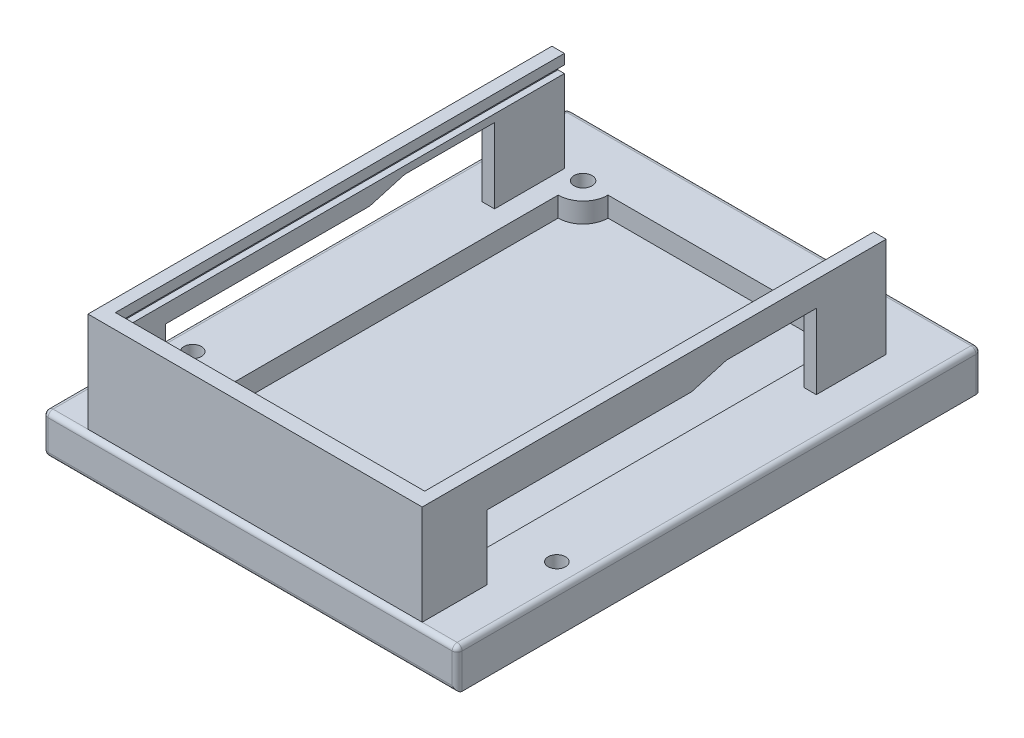
SolidWorks part; units mm, degrees
ref_plane "Front Plane" through (0, 0, 0) normal (0, 0, 1) x (1, 0, 0)
ref_plane "Top Plane" through (0, 0, 0) normal (0, 1, 0) x (1, 0, 0)
ref_plane "Right Plane" through (0, 0, 0) normal (1, 0, 0) x (0, 0, -1)
sketch "Sketch1" plane through (0, 0, 0) normal (0, 1, 0) x (1, 0, 0)
  line L0 (41.5, 95) -> (41.5, 0) construction
  line L1 (0, 0) -> (83, 0)
  line L2 (0, 0) -> (0, 105)
  line L3 (0, 105) -> (83, 105)
  line L4 (83, 0) -> (83, 105)
  line L5 (14.475, 93.775) -> (14.475, 11.225) construction
  circle A0 centre (5, 25) radius 1.75
  circle A1 centre (14.475, 11.225) radius 1.65 construction
  circle A2 centre (14.475, 93.775) radius 1.65 construction
  circle A3 centre (78, 25) radius 1.75
  circle A4 centre (68.525, 11.225) radius 1.65 construction
  circle A5 centre (68.525, 93.775) radius 1.65 construction
  point P19 (14.475, 52.5)
  point P20 (41.5, 0)
  point P21 (0, 52.5)
  dimension "D2" = 36.5
  dimension "D3" = 3.5
  dimension "D5" = 13.775
  dimension "D6" = 27.025
  dimension "D7" = 3.3
  dimension "D9" = 82.55
  dimension "D10" = 3.3
  dimension "D1" = 83
  dimension "D4" = 105
extrude "Boss-Extrude1" add sketch "Sketch1" along normal blind 8
sketch "Sketch3" plane through (0, 0, 0) normal (0, -1, 0) x (1, 0, 0)
  point P0 (14.475, -11.225)
  point P1 (68.525, -11.225)
  point P3 (68.525, -93.775)
  point P5 (14.475, -93.775)
hole_wizard "CBORE for M3 SHCS1" positions "Sketch3" profile "Sketch4" counterbore size "M3" standard "ANSI Metric" end condition through all
sketch "Sketch4" plane through (14.475, 0, -11.225) normal (1, 0, 0) x (0, 0, -1)
  line L0 (0, 0) -> (0, 8)
  line L1 (0, 8) -> (1.8, 8)
  line L3 (1.8, 8) -> (1.8, 3)
  line L4 (1.8, 3) -> (3.25, 3)
  line L5 (3.25, 3) -> (3.25, 0)
  line L7 (3.25, 0) -> (0, 0)
  line L11 (0, -6.35) -> (0, 107.95) construction
  dimension "Thru Hole Dia." = 3.6
  dimension "Thru Hole Depth" = 8
  dimension "C'Bore Dia." = 6.5
  dimension "C'Bore Depth" = 3
sketch "Sketch5" plane through (0, 8, 0) normal (0, 1, 0) x (1, 0, 0)
  line L1 (19.475, 93.775) -> (63.525, 93.775)
  line L2 (14.475, 88.775) -> (14.475, 16.225)
  line L3 (19.475, 11.225) -> (63.525, 11.225)
  line L4 (68.525, 88.775) -> (68.525, 16.225)
  line L5 (41.5, 200095) -> (41.5, -200000) construction
  circle A0 centre (14.475, 93.775) radius 1.65 construction
  circle A1 centre (14.475, 11.225) radius 1.65 construction
  arc A3 (14.475, 88.775) -> (19.475, 93.775) centre (14.475, 93.775) ccw
  arc A4 (63.525, 93.775) -> (68.525, 88.775) centre (68.525, 93.775) ccw
  arc A5 (68.525, 16.225) -> (63.525, 11.225) centre (68.525, 11.225) ccw
  arc A6 (19.475, 11.225) -> (14.475, 16.225) centre (14.475, 11.225) ccw
  dimension "D3" = 54.05
  dimension "D4" = 27.025
  dimension "D1" = 0
  dimension "D2" = 0
extrude "Cut-Extrude1" cut sketch "Sketch5" against normal blind 4
sketch "Sketch6" plane through (0, 0, 0) normal (0, -1, 0) x (1, 0, 0)
  line L1 (11.475, -40) -> (16.475, -40)
  line L2 (11.475, -40) -> (11.475, -60)
  line L3 (11.475, -60) -> (16.475, -60)
  line L4 (16.475, -40) -> (16.475, -60)
  dimension "D1" = 5
  dimension "D2" = 20
  dimension "D3" = 3
  dimension "D4" = 15
extrude "Boss-Extrude2" add sketch "Sketch6" along normal blind 8.8
sketch "Sketch7" plane through (0, 0, -60) normal (0, 0, -1) x (-1, 0, 0)
  line L0 (-16.475, -8.8) -> (-16.475, 0) construction
  line L1 (-11.475, 0) -> (-14.675, 0)
  line L2 (-11.475, 0) -> (-11.475, -6.8)
  line L3 (-11.475, -6.8) -> (-14.675, -6.8)
  line L4 (-14.675, 0) -> (-14.675, -6.8)
  dimension "D1" = 6.8
  dimension "D2" = 1.8
extrude "Cut-Extrude2" cut sketch "Sketch7" against normal through all
fillet "Fillet1" radius 6 1 edges at (16.475, 0, -50) second distance 8 first distance on face at (14.475, 0, -14.475)
fillet "Fillet2" radius 1 10 edges at (0, 4, 0) (41.5, 8, 0) (83, 4, 0) (83, 4, -105) (83, 8, -52.5) (41.5, 8, -105) (0, 4, -105) (0, 8, -52.5) (0, 0, -52.5) (41.5, 0, 0)
sketch "Sketch8" plane through (0, 8, 0) normal (0, 1, 0) x (1, 0, 0)
  line L1 (8, 94) -> (75, 94)
  line L2 (8, 94) -> (8, 1)
  line L3 (8, 1) -> (75, 1)
  line L4 (75, 94) -> (75, 1)
  line L6 (1, 1) -> (82, 1) construction
  circle A4 centre (5, 25) radius 1.75 construction
  dimension "D1" = 3
  dimension "D3" = 93
  dimension "D2" = 3
  dimension "D4" = 0
extrude "Boss-Extrude4" add sketch "Sketch8" along normal blind 20
sketch "Sketch11" plane through (0, 0, -94) normal (0, 0, -1) x (-1, 0, 0)
  line L0 (-75, 8) -> (-70.3109, 8) construction
  line L1 (-72.5, 8) -> (-10.5, 8)
  line L2 (-72.5, 8) -> (-72.5, 24.5)
  line L3 (-72.5, 28) -> (-10.5, 28)
  line L4 (-10.5, 8) -> (-10.5, 24.5)
  line L5 (-75, 28) -> (-75, 8) construction
  line L6 (-8, 28) -> (-8, 8) construction
  line L7 (-75, 28) -> (-8, 28) construction
  line L8 (-10.5, 24.5) -> (-9.2, 24.5)
  line L9 (-73.8, 26) -> (-72.5, 26)
  line L10 (-73.8, 26) -> (-73.8, 24.5)
  line L11 (-73.8, 24.5) -> (-72.5, 24.5)
  line L12 (-9.2, 26) -> (-9.2, 24.5)
  line L13 (-10.5, 26) -> (-9.2, 26)
  line L14 (-72.5, 26) -> (-72.5, 28)
  line L15 (-10.5, 26) -> (-10.5, 28)
  dimension "D1" = 2.5
  dimension "D2" = 2.5
  dimension "D3" = 0
  dimension "D4" = 1.2
  dimension "D5" = 1.5
  dimension "D6" = 1.2
  dimension "D7" = 2
extrude "Cut-Extrude3" cut sketch "Sketch11" against normal blind 90
sketch "Sketch12" plane through (0, 0, -4) normal (0, 0, -1) x (-1, 0, 0)
  line L1 (-73.8, 26) -> (-9.2, 26)
  line L2 (-73.8, 26) -> (-73.8, 24.5)
  line L3 (-73.8, 24.5) -> (-9.2, 24.5)
  line L4 (-9.2, 26) -> (-9.2, 24.5)
extrude "Cut-Extrude4" cut sketch "Sketch12" against normal blind 1
sketch "Sketch15" plane through (75, 0, 0) normal (1, 0, 0) x (0, 0, -1)
  line L0 (1, 8) -> (104, 8) construction
  line L1 (55, 8) -> (37, 8)
  line L2 (55, 8) -> (55, 21) construction
  line L3 (55, 21) -> (37, 21)
  line L4 (37, 8) -> (37, 21) construction
  line L5 (32, 21) -> (37, 21)
  line L6 (1, 8) -> (94, 8) construction
  line L7 (32, 8) -> (14, 8)
  line L8 (32, 8) -> (32, 21) construction
  line L9 (32, 21) -> (14, 21)
  line L10 (14, 8) -> (14, 21)
  line L11 (1, 28) -> (1, 8) construction
  line L12 (32, 8) -> (37, 8)
  line L13 (55, 21) -> (62, 23)
  line L14 (62, 23) -> (80, 23)
  line L15 (62, 23) -> (62, 8) construction
  line L16 (62, 8) -> (80, 8)
  line L17 (80, 23) -> (80, 8)
  line L18 (55, 8) -> (62, 8)
  dimension "D1" = 18
  dimension "D2" = 13
  dimension "D3" = 13
  dimension "D4" = 18
  dimension "D5" = 13
  dimension "D6" = 5
  dimension "D7" = 18
  dimension "D8" = 15
  dimension "D9" = 7
extrude "Cut-Extrude5" cut sketch "Sketch15" against normal through all and the other way through all
